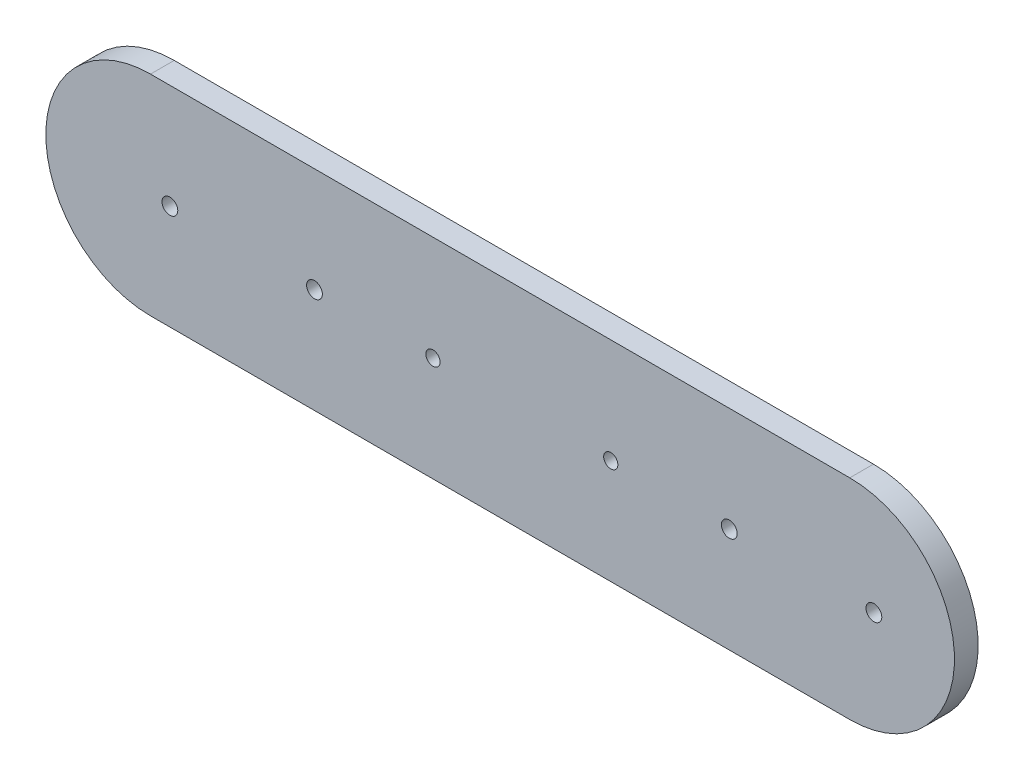
SolidWorks part; units mm, degrees
material "Balsa"
ref_plane "Plano frontal" through (0, 0, 0) normal (0, 0, 1) x (1, 0, 0)
ref_plane "Plano superior" through (0, 0, 0) normal (0, 1, 0) x (1, 0, 0)
ref_plane "Plano direito" through (0, 0, 0) normal (1, 0, 0) x (0, 0, -1)
sketch "Esboço1" plane through (0, 0, 0) normal (0, 0, 1) x (1, 0, 0)
  line L0 (-94, 26.5) -> (83, 26.5)
  line L1 (-94, -26.5) -> (83, -26.5)
  line L2 (-94, 0) -> (-20.7, 0) construction
  line L3 (-22.5, 0) -> (22.5, 0) construction
  line L4 (0, 11.6249) -> (0, -21.7831) construction
  line L5 (20.7, 0) -> (22.5, 0) construction
  arc A0 (83, -26.5) -> (83, 26.5) centre (83, 0) ccw
  arc A1 (-94, 26.5) -> (-94, -26.5) centre (-94, 0) ccw
  circle A4 centre (-22.5, 0) radius 1.8
  circle A5 centre (22.5, 0) radius 1.8
  circle A6 centre (-89.1, 0) radius 2
  circle A7 centre (-52.5, 0) radius 2
  circle A8 centre (52.5, 0) radius 2
  circle A9 centre (89.1, 0) radius 2
  point P19 (0, 0)
  dimension "D1" = 3.6
  dimension "D6" = 26.5
  dimension "D7" = 4
  dimension "D2" = 45
  dimension "D3" = 83
  dimension "D4" = 94
  dimension "D8" = 36.6
  dimension "D9" = 30
extrude "Ressalto-extrusão1" add sketch "Esboço1" along normal blind 6
